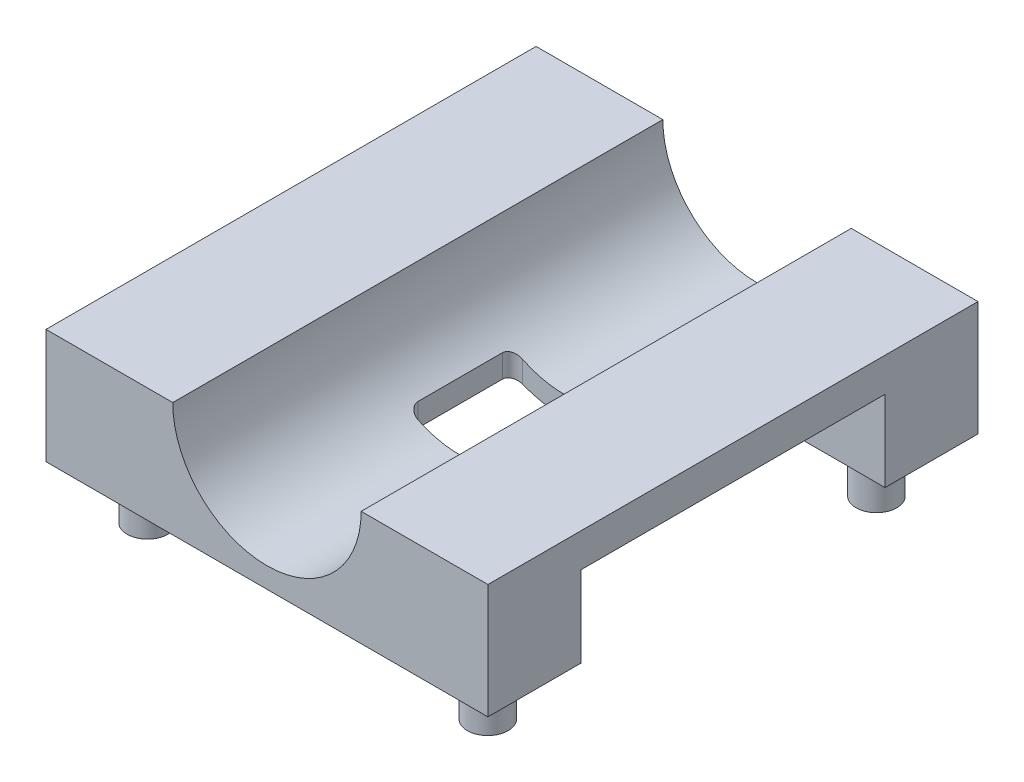
SolidWorks part; units mm, degrees
ref_plane "Front Plane" through (0, 0, 0) normal (0, 0, 1) x (1, 0, 0)
ref_plane "Top Plane" through (0, 0, 0) normal (0, 1, 0) x (1, 0, 0)
ref_plane "Right Plane" through (0, 0, 0) normal (1, 0, 0) x (0, 0, -1)
sketch "Sketch1" plane through (0, 0, 0) normal (0, 0, 1) x (1, 0, 0)
  line L0 (0, 22.5039) -> (0, -15.5254) construction
  line L2 (-28.0176, 0) -> (26.9335, 0) construction
  line L4 (5.575, 9.9357) -> (13.075, 9.9357)
  line L5 (13.075, 9.9357) -> (13.075, 3.1518)
  line L6 (13.075, 3.1518) -> (-13.075, 3.1518)
  line L7 (-13.075, 3.1518) -> (-13.075, 9.9357)
  line L8 (-13.075, 9.9357) -> (-5.575, 9.9357)
  arc A0 (-5.575, 9.9357) -> (5.575, 9.9357) centre (0, 9.9357) ccw
  point P11 (0, 0)
  point P18 (0, 0)
  point P19 (0, 0)
  dimension "D1" = 7.5
extrude "Boss-Extrude1" add sketch "Sketch1" along normal blind 14.5 and the other way blind 14.5 contours L8 A0 L4 L5 L6 L7
sketch "Sketch2" plane through (0, 0, 0) normal (0, 1, 0) x (1, 0, 0)
  circle A1 centre (10.105, 11.46) radius 1.205
  circle A2 centre (10.0266, -11.46) radius 1.205
  circle A3 centre (-10.105, -11.46) radius 1.205
  circle A4 centre (-10.105, 11.46) radius 1.205
extrude "Boss-Extrude2" add sketch "Sketch2" along normal up to surface (3.1518 mm away) up to face at (0, 3.1518, 0)
sketch "Sketch3" plane through (0, 0, 0) normal (0, 1, 0) x (1, 0, 0)
  line L1 (-2.4451, 3.0774) -> (2.3914, 3.0774)
  line L2 (-3.0451, 2.4774) -> (-3.0451, -2.5169)
  line L3 (-2.4451, -3.1169) -> (2.3914, -3.1169)
  line L4 (2.9914, 2.4774) -> (2.9914, -2.5169)
  arc A0 (-3.0451, -2.5169) -> (-2.4451, -3.1169) centre (-2.4451, -2.5169) ccw
  arc A1 (2.3914, -3.1169) -> (2.9914, -2.5169) centre (2.3914, -2.5169) ccw
  arc A2 (2.3914, 3.0774) -> (2.9914, 2.4774) centre (2.3914, 2.4774) cw
  arc A3 (-2.4451, 3.0774) -> (-3.0451, 2.4774) centre (-2.4451, 2.4774) ccw
  dimension "D1" = 0.6
extrude "Cut-Extrude1" cut sketch "Sketch3" against normal blind 10 from surface contours L3 A1 L4 A2 L1 A3 L2 A0 starting at face at (-9.325, 9.9357, 0)
sketch "Sketch5" plane through (0, 0, 0) normal (0, 0, 1) x (1, 0, 0)
  line L0 (-6.4502, 7.9357) -> (-13.075, 7.9357)
  line L1 (-13.075, 3.1518) -> (-13.075, 9.9357) construction
  line L2 (-13.075, 7.9357) -> (-13.075, 3.1518)
  line L5 (13.075, 3.1518) -> (13.075, 7.9357)
  line L6 (13.075, 9.9357) -> (13.075, 3.1518) construction
  line L7 (13.075, 7.9357) -> (6.4502, 7.9357)
  line L8 (-13.075, 9.9357) -> (-5.575, 9.9357) construction
  line L9 (5.575, 9.9357) -> (13.075, 9.9357) construction
  line L10 (-13.075, 3.1518) -> (13.075, 3.1518)
  arc A0 (-6.4502, 7.9357) -> (6.4502, 7.9357) centre (0, 9.9357) ccw
  arc A3 (-5.575, 9.9357) -> (5.575, 9.9357) centre (0, 9.9357) ccw construction
  dimension "D1" = 2
  dimension "D2" = 2
extrude "Cut-Extrude2" cut sketch "Sketch5" against normal blind 9 and the other way blind 9
